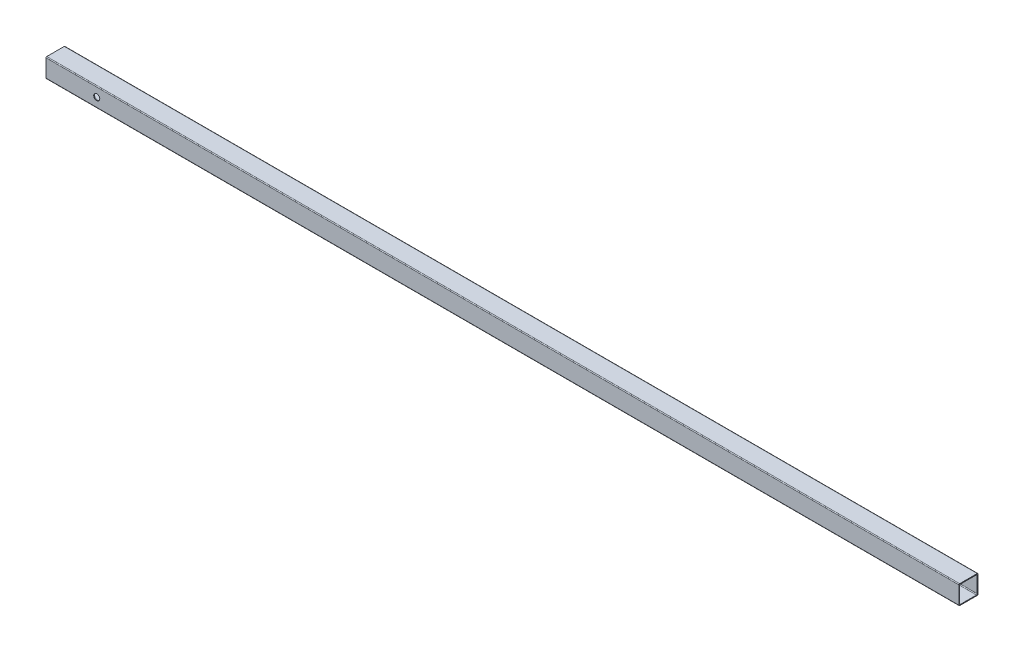
SolidWorks part; units mm, degrees
material "Thornel Mat VMA"
ref_plane "Front Plane" through (0, 0, 0) normal (0, 0, 1) x (1, 0, 0)
ref_plane "Top Plane" through (0, 0, 0) normal (0, 1, 0) x (1, 0, 0)
ref_plane "Right Plane" through (0, 0, 0) normal (1, 0, 0) x (0, 0, -1)
sketch "Sketch2" plane through (0, 0, 0) normal (1, 0, 0) x (0, 0, -1)
  line L1 (0.762, 0) -> (18.288, 0)
  line L2 (0, 0.762) -> (0, 18.288)
  line L3 (0.762, 19.05) -> (18.288, 19.05)
  line L4 (19.05, 0.762) -> (19.05, 18.288)
  line L5 (1.524, 0.762) -> (17.526, 0.762)
  line L6 (0.762, 1.524) -> (0.762, 17.526)
  line L7 (1.524, 18.288) -> (17.526, 18.288)
  line L8 (18.288, 1.524) -> (18.288, 17.526)
  arc A0 (17.526, 18.288) -> (18.288, 17.526) centre (17.526, 17.526) cw
  arc A1 (17.526, 0.762) -> (18.288, 1.524) centre (17.526, 1.524) ccw
  arc A2 (1.524, 0.762) -> (0.762, 1.524) centre (1.524, 1.524) cw
  arc A3 (0.762, 17.526) -> (1.524, 18.288) centre (1.524, 17.526) cw
  arc A4 (18.288, 19.05) -> (19.05, 18.288) centre (18.288, 18.288) cw
  arc A5 (18.288, 0) -> (19.05, 0.762) centre (18.288, 0.762) ccw
  arc A6 (0.762, 0) -> (0, 0.762) centre (0.762, 0.762) cw
  arc A7 (0, 18.288) -> (0.762, 19.05) centre (0.762, 18.288) cw
  point P11 (18.288, 18.288)
  point P14 (18.288, 0.762)
  point P19 (0.762, 18.288)
  point P22 (19.05, 19.05)
  point P25 (19.05, 0)
  point P28 (0, 0)
  point P31 (0, 19.05)
  dimension "D7" = 0.762
  dimension "D1" = 19.05
  dimension "D2" = 19.05
  dimension "D5" = 0.762
  dimension "D6" = 0.762
  dimension "D3" = 0.762
  dimension "D4" = 0.762
extrude "Boss-Extrude1" add sketch "Sketch2" along normal blind 914.4
sketch "Sketch3" plane through (0, 0, 0) normal (0, 0, 1) x (1, 0, 0)
  line L0 (0, 18.288) -> (0, 0.762) construction
  line L1 (914.4, 19.05) -> (0, 19.05) construction
  circle A0 centre (50.8, 9.525) radius 3.048
  dimension "D1" = 6.096
  dimension "D2" = 50.8
  dimension "D3" = 9.525
extrude "Cut-Extrude1" cut sketch "Sketch3" against normal up to surface (19.05 mm away) up to face at (457.2, 9.525, -19.05)
equation "\"shaft\"=0.75"
equation "\"D1@Sketch2\"=\"shaft\""
equation "\"D2@Sketch2\"=\"shaft\""
equation "\"IDshaft\"=0.4375"
equation "\"D3@Sketch3\"=\"shaft\"/2"
